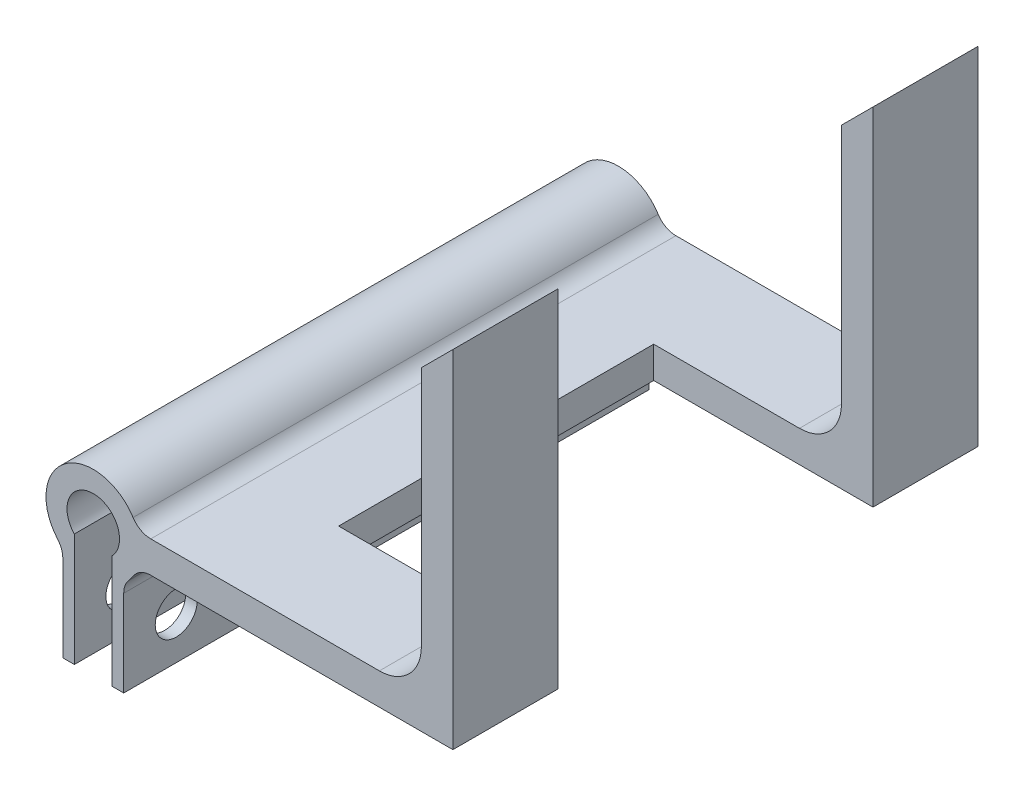
SolidWorks part; units mm, degrees
ref_plane "前视基准面" through (0, 0, 0) normal (0, 0, 1) x (1, 0, 0)
ref_plane "上视基准面" through (0, 0, 0) normal (0, 1, 0) x (1, 0, 0)
ref_plane "右视基准面" through (0, 0, 0) normal (1, 0, 0) x (0, 0, -1)
sketch "草图1" plane through (0, 0, 0) normal (0, 0, 1) x (1, 0, 0)
  circle A0 centre (0, 0) radius 1.25
  circle A1 centre (0, 0) radius 2.25
  dimension "D1" = 2.5
  dimension "D2" = 4.5
extrude "凸台-拉伸1" add sketch "草图1" along normal blind 25
sketch "草图2" plane through (0, 0, 25) normal (0, 0, 1) x (1, 0, 0)
  line L5 (-0.9, 2.0154) -> (0.9, 2.0154)
  line L6 (-0.9, 2.0154) -> (-0.9, -4.5154)
  line L11 (-0.9, -4.5154) -> (0.9, -4.5154)
  line L12 (0.9, 2.0154) -> (0.9, -4.5154)
  line L13 (0, -4.5154) -> (0, 2.0154) construction
  line L14 (-0.9, -1.25) -> (0.9, -1.25) construction
  line L15 (-1.45, 1.75) -> (1.45, 1.75)
  line L16 (-1.45, 1.75) -> (-1.45, -4.25)
  line L17 (-1.45, -4.25) -> (1.45, -4.25)
  line L18 (1.45, 1.75) -> (1.45, -4.25)
  line L19 (0, -4.25) -> (0, 1.75) construction
  line L20 (-1.45, -1.25) -> (1.45, -1.25) construction
  circle A1 centre (0, 0) radius 1.25 construction
  point P0 (0, -1.25)
  point P6 (0, -1.25)
  circle M13 centre (0, 0) radius 2.25
  dimension "D1" = 1.8
  dimension "D2" = 2.9
  dimension "D3" = 6
extrude "凸台-拉伸2" add sketch "草图2" against normal blind 25 contours L16 L17 L6 M13 | L18 L12 L17 M13 region at (-1.1817, -3.0778, 25) region at (1.1817, -3.0778, 25)
sketch "草图3" plane through (0, 0, 25) normal (0, 0, 1) x (1, 0, 0)
  line L0 (-0.9, -2.0622) -> (-0.9, -0.6082)
  line L1 (0.9, -2.0622) -> (0.9, -0.5726)
  line L2 (0.9, -0.5726) -> (-0.9, -0.6082)
  line L3 (-0.9, -2.0622) -> (-0.2203, -2.7115)
  line L4 (-0.2203, -2.7115) -> (0.9, -2.0622)
extrude "切除-拉伸1" cut sketch "草图3" against normal blind 25
sketch "草图4" plane through (0, -4.25, 0) normal (0, -1, 0) x (1, 0, 0)
  line L0 (1.45, 25) -> (0.9, 25) construction
  line L1 (0.9, 25) -> (0.9, 0) construction
  line L2 (0.9, 0) -> (1.45, 0) construction
  line L3 (1.45, 0) -> (1.45, 25) construction
  line L4 (-0.9, 25) -> (-1.45, 25) construction
  line L5 (-1.45, 25) -> (-1.45, 0) construction
  line L6 (-1.45, 0) -> (-0.9, 0) construction
  line L7 (-0.9, 0) -> (-0.9, 25) construction
  line L8 (1.45, 25) -> (0.9, 25)
  line L9 (0.9, 25) -> (0.9, 0)
  line L10 (0.9, 0) -> (1.45, 0)
  line L11 (1.45, 0) -> (1.45, 25)
  line L12 (-0.9, 25) -> (-1.45, 25)
  line L13 (-1.45, 25) -> (-1.45, 0)
  line L14 (-1.45, 0) -> (-0.9, 0)
  line L15 (-0.9, 0) -> (-0.9, 25)
extrude "凸台-拉伸3" add sketch "草图4" along normal blind 2
sketch "草图5" plane through (0, 0, 25) normal (0, 0, 1) x (1, 0, 0)
  line L0 (2.1213, 0.75) -> (17.1213, 0.75)
  line L1 (0, 0) -> (5.89, 0) construction
  line L2 (2.1213, -0.75) -> (17.1213, -0.75)
  line L3 (17.1213, 0.75) -> (17.1213, -0.75)
  arc A0 (1.45, -1.7205) -> (-1.45, -1.7205) centre (0, 0) ccw construction
  arc A1 (2.1213, 0.75) -> (2.1213, -0.75) centre (0, 0) cw
  dimension "D1" = 15
  dimension "D2" = 1.5
extrude "凸台-拉伸4" add sketch "草图5" against normal blind 25
fillet "圆角1" radius 1 4 edges at (-1.45, -1.7205, 12.5) (1.45, -1.7205, 12.5) (2.1213, -0.75, 12.5) (2.1213, 0.75, 12.5)
sketch "草图6" plane through (0, 0.75, 0) normal (0, 1, 0) x (1, 0, 0)
  line L0 (17.1213, 0) -> (15.6213, 0)
  line L1 (17.1213, 0) -> (2.7386, 0) construction
  line L2 (15.6213, 0) -> (15.6213, -25)
  line L3 (17.1213, -25) -> (2.7386, -25) construction
  line L4 (15.6213, -25) -> (17.1213, -25)
  line L5 (17.1213, -25) -> (17.1213, 0)
  dimension "D1" = 1.5
extrude "凸台-拉伸6" add sketch "草图6" along normal blind 15
sketch "草图7" plane through (0, 0.75, 0) normal (0, 1, 0) x (1, 0, 0)
  line L0 (15.6213, 0) -> (15.6213, -25) construction
  line L1 (6.6816, -5) -> (24.561, -5)
  line L2 (6.6816, -5) -> (6.6816, -20)
  line L3 (6.6816, -20) -> (24.561, -20)
  line L4 (24.561, -5) -> (24.561, -20)
  line L5 (15.6213, -20) -> (15.6213, -5) construction
  line L6 (6.6816, -12.5) -> (24.561, -12.5) construction
  point P0 (15.6213, -12.5)
  dimension "D1" = 15
extrude "切除-拉伸2" cut sketch "草图7" against normal mid plane 100
fillet "圆角2" radius 2 2 edges at (15.6213, 0.75, 22.5) (15.6213, 0.75, 2.5)
sketch "草图8" plane through (-1.45, 0, 0) normal (-1, 0, 0) x (0, 0, 1)
  line L0 (0, 15.75) -> (5, 15.75) construction
  line L1 (0, -2.1354) -> (0, -6.25) construction
  line L2 (20, 15.75) -> (25, 15.75) construction
  circle A0 centre (2.5, -4.1927) radius 1
  circle A1 centre (22.5, -4.1927) radius 1
  point P4 (2.5, 15.75)
  point P5 (0, 0)
  point P8 (0, -4.1927)
  point P12 (22.5, 15.75)
  dimension "D1" = 2
extrude "切除-拉伸3" cut sketch "草图8" against normal blind 10
chamfer "倒角1" distance 1.5 angle 45 2 edges at (15.6213, 15.75, 2.5) (15.6213, 15.75, 22.5)
